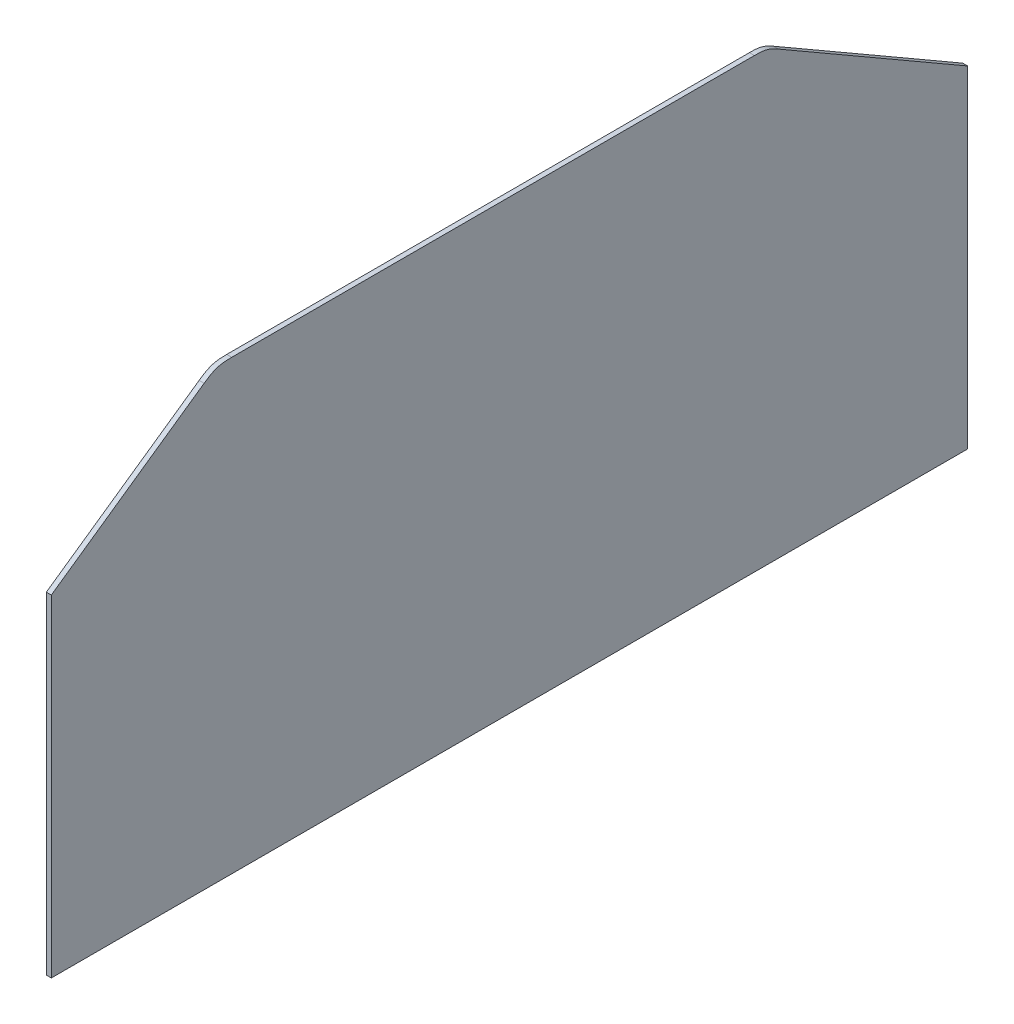
SolidWorks part; units mm, degrees
note: The reader was unsure of these and kept them because the rebuilt part matched: thickness of "Base-Flange1", "Sheet-Metal1".
material "6063-T6"
ref_plane "Front Plane" through (0, 0, 0) normal (0, 0, 1) x (1, 0, 0)
ref_plane "Top Plane" through (0, 0, 0) normal (0, 1, 0) x (1, 0, 0)
ref_plane "Right Plane" through (0, 0, 0) normal (1, 0, 0) x (0, 0, -1)
sketch "Sketch1" plane through (0, 0, 0) normal (1, 0, 0) x (0, 0, -1)
  line L0 (0, 172) -> (85.6889, 232)
  line L1 (0, 0) -> (475.224, 0)
  line L2 (0, 0) -> (0, 172)
  line L4 (475.224, 0) -> (475.224, 172)
  line L5 (85.6889, 232) -> (371.301, 232)
  line L6 (371.301, 232) -> (475.224, 172)
  dimension "D1" = 475.224
  dimension "D2" = 125
  dimension "D3" = 120
  dimension "D4" = 172
  dimension "D5" = 172
  dimension "D6" = 60
base flange "Base-Flange1" sketch "Sketch1" thickness 2.588 reverse thickness direction no parameters "D1"=3
fillet "Fillet1" radius 25 2 edges at (-1.294, 232, -85.6889) (-1.294, 232, -371.301) curvature continuous yes
sketch "Bend-Lines1" [suppressed] plane through (0, 0, 0) normal (0, 1, 0) x (1, 0, 0)
sketch "Bounding-Box1" [suppressed] plane through (0, 0, 0) normal (0, 1, 0) x (1, 0, 0)
sheet metal parameters "Sheet-Metal1" thickness 2.588 parameters "D1"=3, "D7"=3.264
flat pattern "Flat-Pattern1" [suppressed]
sketch "Bend-Lines2" plane through (0, 0, 0) normal (0, 1, 0) x (1, 0, 0)
sketch3d "Bounding-Box2" [suppressed]
  line L0 (475.224, 0, 0) -> (0, 0, 0) construction
  line L1 (475.224, 232, 0) -> (0, 232, 0) construction
  line L2 (475.224, 0, 0) -> (475.224, 232, 0) construction
  line L3 (0, 0, 0) -> (0, 232, 0) construction
